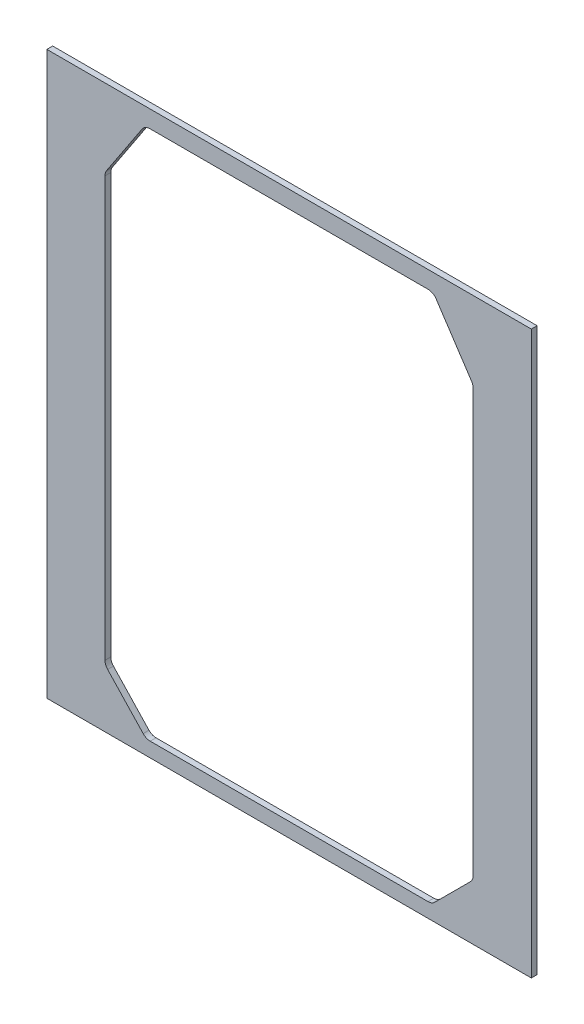
SolidWorks part; units mm, degrees
material "Клен"
ref_plane "Спереди" through (0, 0, 0) normal (0, 0, 1) x (1, 0, 0)
ref_plane "Сверху" through (0, 0, 0) normal (0, 1, 0) x (1, 0, 0)
ref_plane "Справа" through (0, 0, 0) normal (1, 0, 0) x (0, 0, -1)
sketch "Эскиз1" plane through (0, 0, 0) normal (0, 0, 1) x (1, 0, 0)
  line L0 (2.3279, 477.4565) -> (2.3279, 44.4311)
  line L1 (-57.6721, 560.4642) -> (442.3279, 560.4642)
  line L2 (-57.6721, 560.4642) -> (-57.6721, -19.5358)
  line L3 (-57.6721, -19.5358) -> (442.3279, -19.5358)
  line L4 (442.3279, 560.4642) -> (442.3279, -19.5358)
  line L5 (2.3279, 40.4642) -> (192.3279, 40.4642) construction
  line L6 (382.3279, 477.4565) -> (382.3279, 42.1529)
  line L12 (335.7697, 542.7331) -> (48.8861, 542.7331)
  line L13 (192.3279, 560.4642) -> (192.3279, -60.4943) construction
  line L14 (192.3279, 656.9058) -> (192.3279, 661.2918) construction
  line L15 (380.6688, 482.9729) -> (344.1105, 538.2495)
  line L20 (3.9871, 482.9729) -> (40.5453, 538.2495)
  line L22 (335.6393, -4.5358) -> (192.3279, -4.5358)
  line L23 (49.0166, -4.5358) -> (192.3279, -4.5358)
  line L24 (379.399, 35.0818) -> (342.7103, -1.6068)
  line L25 (41.7359, -1.3908) -> (5.0472, 37.5761)
  arc A0 (2.3279, 477.4565) -> (3.9871, 482.9729) centre (12.3279, 477.4565) cw
  arc A1 (48.8861, 542.7331) -> (40.5453, 538.2495) centre (48.8861, 532.7331) ccw
  arc A2 (344.1105, 538.2495) -> (335.7697, 542.7331) centre (335.7697, 532.7331) ccw
  arc A3 (382.3279, 477.4565) -> (380.6688, 482.9729) centre (372.3279, 477.4565) ccw
  arc A4 (2.3279, 44.4311) -> (5.0472, 37.5761) centre (12.3279, 44.4311) ccw
  arc A5 (41.7359, -1.3908) -> (49.0166, -4.5358) centre (49.0166, 5.4642) ccw
  arc A6 (342.7103, -1.6068) -> (335.6393, -4.5358) centre (335.6393, 5.4642) cw
  arc A7 (379.399, 35.0818) -> (382.3279, 42.1529) centre (372.3279, 42.1529) ccw
  point P17 (43.5106, 542.7331)
  point P21 (341.1452, 542.7331)
  dimension "D1" = 10
  dimension "D2" = 10
  dimension "D3" = 60
  dimension "D4" = 380
  dimension "D5" = 60
  dimension "D6" = 60
  dimension "D7" = 15
  dimension "D8" = 45
extrude "Бобышка-Вытянуть1" add sketch "Эскиз1" along normal blind 6
equation "\"sheet_thickness\"= 6"
equation "\"D1@Бобышка-Вытянуть1\"= \"sheet_thickness\""
equation "\"bottom_line\"= 60"
equation "\"width_space\"= 500"
equation "\"D6@Эскиз1\"=\"D5@Эскиз1\""
